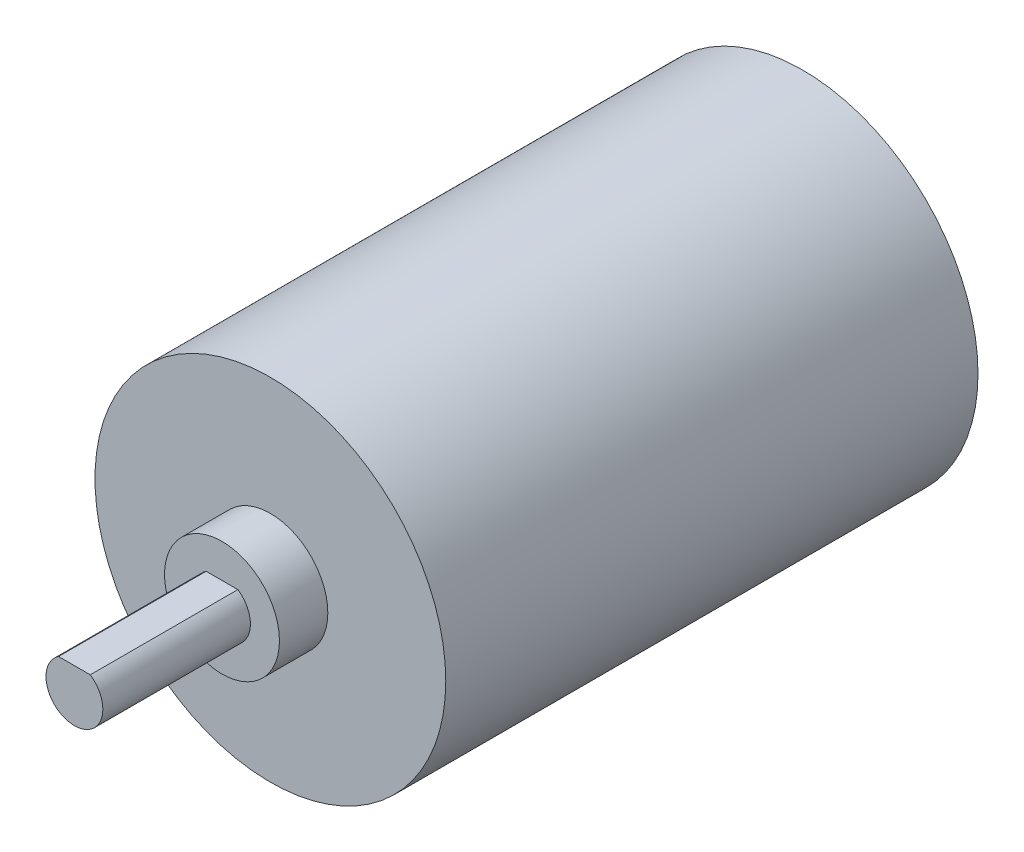
SolidWorks part; units mm, degrees
ref_plane "Front Plane" through (0, 0, 0) normal (0, 0, 1) x (1, 0, 0)
ref_plane "Top Plane" through (0, 0, 0) normal (0, 1, 0) x (1, 0, 0)
ref_plane "Right Plane" through (0, 0, 0) normal (1, 0, 0) x (0, 0, -1)
sketch "Sketch1" plane through (0, 0, 0) normal (0, 0, 1) x (1, 0, 0)
  circle A0 centre (0, 0) radius 18.415
  circle A1 centre (0, 0) radius 6.0325
  dimension "D1" = 36.83
  dimension "D2" = 12.065
extrude "Boss-Extrude1" add sketch "Sketch1" against normal blind 55.88 contours A0
sketch "Sketch2" plane through (0, 0, 0) normal (0, 0, 1) x (1, 0, 0)
extrude "Boss-Extrude2" add sketch "Sketch1<3>" along normal blind 5.08
sketch "Sketch1<3>" plane through (0, 0, 0) normal (0, 0, 1) x (1, 0, 0) same geometry as "Sketch1"
sketch "Sketch3" plane through (0, 0, 5.08) normal (0, 0, 1) x (1, 0, 0)
  line L0 (-1.6656, 2.4765) -> (1.6656, 2.4765)
  arc A0 (-1.6656, 2.4765) -> (1.6656, 2.4765) centre (0, 0) ccw
  dimension "D1" = 5.969
  dimension "D2" = 5.461
extrude "Boss-Extrude3" add sketch "Sketch3" along normal blind 15.494 contours A0 L0
